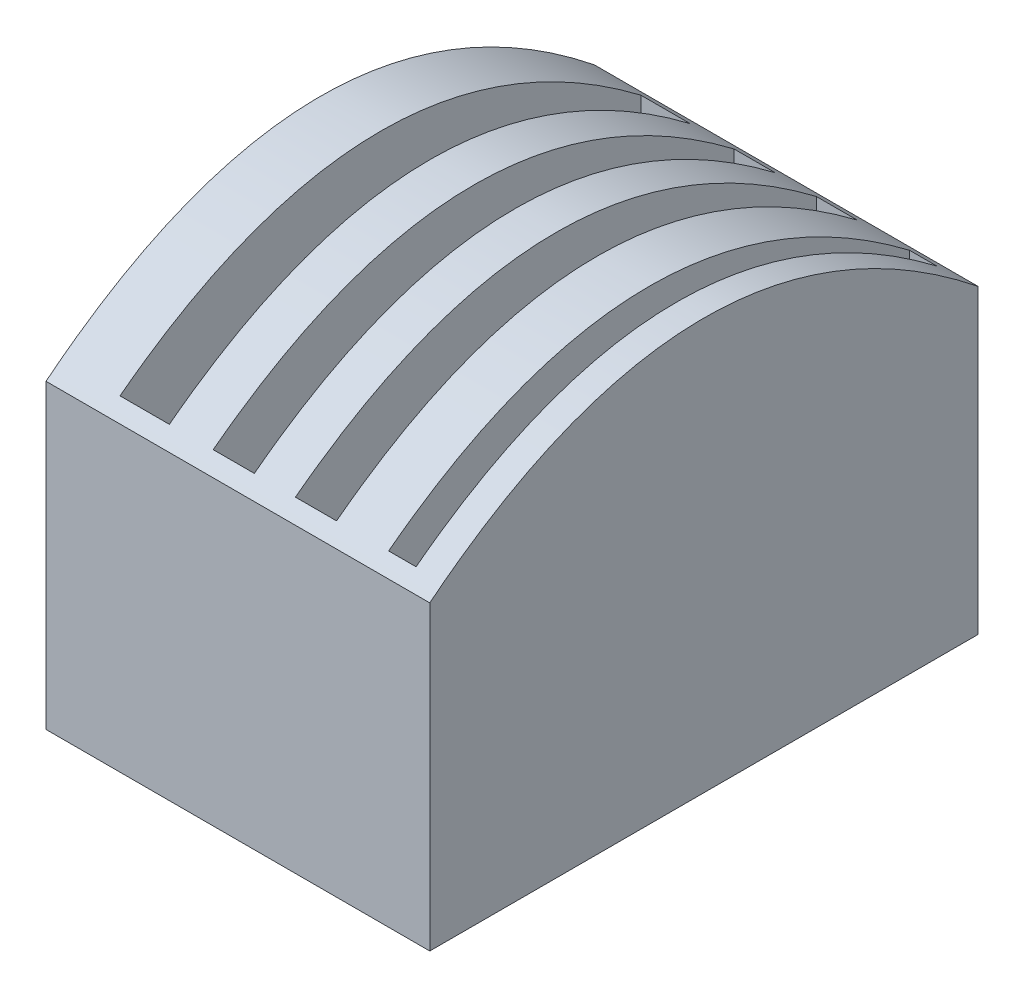
SolidWorks part; units mm, degrees
ref_plane "Front Plane" through (0, 0, 0) normal (0, 0, 1) x (1, 0, 0)
ref_plane "Top Plane" through (0, 0, 0) normal (0, 1, 0) x (1, 0, 0)
ref_plane "Right Plane" through (0, 0, 0) normal (1, 0, 0) x (0, 0, -1)
sketch "Sketch1" plane through (0, 0, 0) normal (1, 0, 0) x (0, 0, -1)
  line L2 (-100, 85) -> (-100, -25)
  line L3 (-100, -25) -> (100, -25)
  line L4 (100, 85) -> (100, -25)
  spline S0 degree 2 poles (-100, 85) (0, 165) (100, 85) knots 0 0 0 1 1 1
  point P4 (-100, 85)
  point P5 (100, 85)
  dimension "D1" = 200
  dimension "D2" = 100
  dimension "D3" = 110
  dimension "D4" = 110
  dimension "D5" = 40
  dimension "D6" = 100
  dimension "D7" = 125
extrude "Base" add sketch "Sketch1" along normal blind 140
ref_plane "New Top" through (0, 125, 0) normal (0, 1, 0) x (1, 0, 0)
sketch "Sketch3" plane through (0, 125, 0) normal (0, 1, 0) x (1, 0, 0)
  line L1 (101, 95) -> (86, 95)
  line L2 (101, 95) -> (101, -95)
  line L3 (101, -95) -> (86, -95)
  line L4 (86, 95) -> (86, -95)
  line L7 (140, 100) -> (0, 100) construction
  line L8 (71, 95) -> (56, 95)
  line L9 (71, 95) -> (71, -95)
  line L10 (71, -95) -> (56, -95)
  line L11 (56, 95) -> (56, -95)
  line L12 (140, -100) -> (0, -100) construction
  line L13 (0, 100) -> (0, -100) construction
  dimension "D1" = 56
  dimension "D2" = 15
  dimension "D3" = 15
  dimension "D4" = 15
  dimension "D5" = 5
  dimension "D6" = 5
  dimension "D7" = 5
  dimension "D8" = 5
sketch "Sketch4" plane through (0, 125, 0) normal (0, 1, 0) x (1, 0, 0)
  line L1 (40, 95) -> (22, 95)
  line L2 (40, 95) -> (40, -95)
  line L3 (40, -95) -> (22, -95)
  line L4 (22, 95) -> (22, -95)
  line L5 (140, 100) -> (0, 100) construction
  line L6 (140, -100) -> (0, -100) construction
  line L7 (0, 100) -> (0, -100) construction
  dimension "D1" = 22
  dimension "D2" = 18
  dimension "D3" = 5
  dimension "D4" = 5
sketch "Sketch5" plane through (0, 125, 0) normal (0, 1, 0) x (1, 0, 0)
  line L0 (140, -100) -> (140, 100) construction
  line L1 (130, 95) -> (120, 95)
  line L2 (130, 95) -> (130, -95)
  line L3 (130, -95) -> (120, -95)
  line L4 (120, 95) -> (120, -95)
  line L5 (140, 100) -> (0, 100) construction
  line L6 (140, -100) -> (0, -100) construction
  dimension "D1" = 10
  dimension "D2" = 10
  dimension "D3" = 5
  dimension "D4" = 5
extrude "Flaps Cut" cut sketch "Sketch5" against normal up to surface (150 mm away) up to face at (70, -25, 0)
extrude "Throttle Cut" cut sketch "Sketch3" against normal up to surface (150 mm away) up to face at (125, -25, 0)
extrude "Wing Sweep Cut" cut sketch "Sketch4" against normal up to surface (150 mm away) up to face at (93.5, -25, 0)
